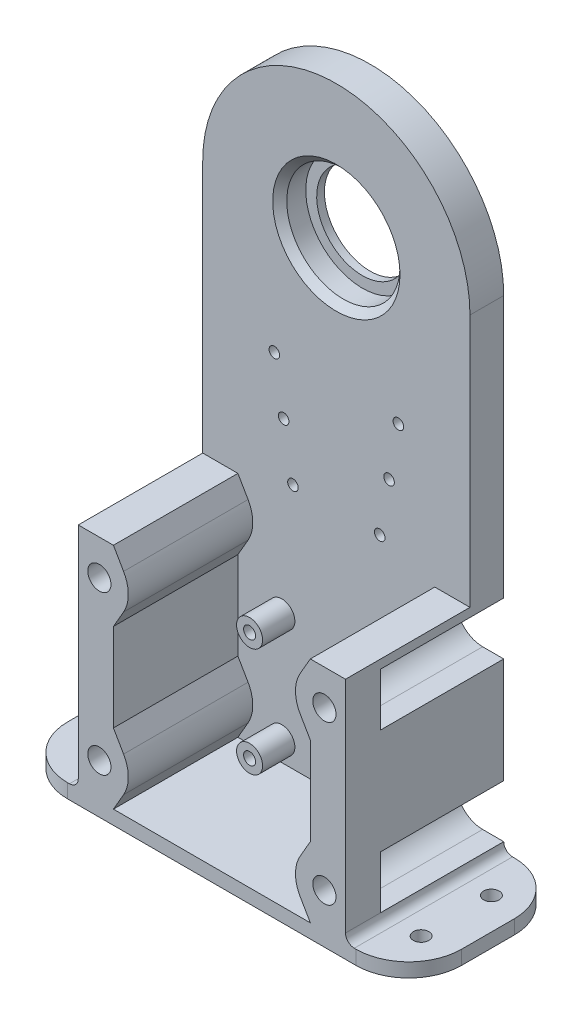
SolidWorks part; units mm, degrees
ref_plane "Ebene vorne" through (0, 0, 0) normal (0, 0, 1) x (1, 0, 0)
ref_plane "Ebene oben" through (0, 0, 0) normal (0, 1, 0) x (1, 0, 0)
ref_plane "Ebene rechts" through (0, 0, 0) normal (1, 0, 0) x (0, 0, -1)
sketch "Skizze1" plane through (0, 0, 0) normal (1, 0, 0) x (0, 0, -1)
  line L1 (-22.5, 65) -> (22.5, 65)
  line L2 (-22.5, 65) -> (-22.5, 0)
  line L3 (-22.5, 0) -> (22.5, 0)
  line L4 (22.5, 65) -> (22.5, 0)
  point P4 (0, 0)
  dimension "D1" = 45
  dimension "D2" = 65
extrude "Aufsatz-Linear austragen1" add sketch "Skizze1" along normal mid plane 76
sketch "Skizze2" plane through (0, 0, 22.5) normal (0, 0, 1) x (1, 0, 0)
  line L0 (-38, 0) -> (-28, 0)
  line L1 (38, 0) -> (-38, 0) construction
  line L2 (-28, 0) -> (-22.2265, 10)
  line L3 (-22.2265, 10) -> (-28, 20)
  line L4 (-28, 20) -> (-28, 45)
  line L5 (-28, 45) -> (-22.2265, 55)
  line L6 (-22.2265, 55) -> (-28, 65)
  line L7 (38, 65) -> (-38, 65) construction
  line L8 (-28, 65) -> (-38, 65)
  line L9 (-38, 65) -> (-38, 0)
  line L10 (-38, 32.5) -> (38, 32.5) construction
  line L11 (38, 65) -> (38, 0) construction
  line L12 (-28, 20) -> (-28, 0) construction
  line L13 (0, 0) -> (0, 65) construction
  line L14 (28, 20) -> (28, 0) construction
  line L15 (38, 65) -> (38, 0)
  line L16 (28, 65) -> (38, 65)
  line L17 (22.2265, 55) -> (28, 65)
  line L18 (28, 45) -> (22.2265, 55)
  line L19 (28, 20) -> (28, 45)
  line L20 (22.2265, 10) -> (28, 20)
  line L21 (28, 0) -> (22.2265, 10)
  line L22 (38, 0) -> (28, 0)
  point P18 (-28, 32.5)
  dimension "D1" = 25
  dimension "D2" = 120
  dimension "D3" = 10
extrude "Schnitt-Linear austragen1" cut sketch "Skizze2" against normal blind 35.4 flip side to cut
sketch "Skizze3" plane through (0, 0, -22.5) normal (0, 0, -1) x (-1, 0, 0)
  line L0 (-32, 17.5) -> (-38, 17.5)
  line L1 (-38, 0) -> (-38, 65) construction
  line L2 (-32, 2.5) -> (-38, 2.5)
  line L3 (-38, 0) -> (38, 0) construction
  line L4 (-38, 17.5) -> (-38, 2.5)
  line L5 (0, 0) -> (0, 65) construction
  line L6 (-38, 65) -> (38, 65) construction
  line L7 (-38, 32.5) -> (38, 32.5) construction
  line L8 (38, 0) -> (38, 65) construction
  line L9 (38, 17.5) -> (38, 2.5)
  line L10 (32, 2.5) -> (38, 2.5)
  line L11 (32, 17.5) -> (38, 17.5)
  line L12 (32, 47.5) -> (38, 47.5)
  line L13 (32, 62.5) -> (38, 62.5)
  line L14 (38, 47.5) -> (38, 62.5)
  line L15 (-38, 47.5) -> (-38, 62.5)
  line L16 (-32, 62.5) -> (-38, 62.5)
  line L17 (-32, 47.5) -> (-38, 47.5)
  arc A0 (-32, 2.5) -> (-32, 17.5) centre (-32, 10) ccw
  arc A1 (32, 2.5) -> (32, 17.5) centre (32, 10) cw
  arc A2 (32, 62.5) -> (32, 47.5) centre (32, 55) ccw
  arc A3 (-32, 62.5) -> (-32, 47.5) centre (-32, 55) cw
  dimension "D1" = 10
  dimension "D2" = 15
  dimension "D3" = 6
extrude "Schnitt-Linear austragen2" cut sketch "Skizze3" against normal blind 35
sketch "Skizze4" plane through (0, 0, 12.5) normal (0, 0, -1) x (-1, 0, 0)
  line L0 (0, 0) -> (0, 65) construction
  line L1 (-38, 0) -> (38, 0) construction
  line L2 (-38, 65) -> (38, 65) construction
  line L3 (-38, 32.5) -> (38, 32.5) construction
  line L4 (-38, 17.5) -> (-38, 47.5) construction
  line L5 (38, 17.5) -> (38, 47.5) construction
  circle A0 centre (32, 10) radius 3.3
  circle A1 centre (-32, 10) radius 3.3
  circle A2 centre (-32, 55) radius 3.3
  circle A3 centre (32, 55) radius 3.3
  dimension "D1" = 6.6
extrude "Schnitt-Linear austragen3" cut sketch "Skizze4" against normal through all
sketch "Skizze5" plane through (0, 0, -12.9) normal (0, 0, 1) x (1, 0, 0)
  line L0 (-38, 65) -> (38, 65)
  line L1 (38, 65) -> (38, 137)
  line L2 (-38, 137) -> (-38, 65)
  arc A0 (38, 137) -> (-38, 137) centre (0, 137) ccw
  dimension "D1" = 110
extrude "Aufsatz-Linear austragen2" add sketch "Skizze5" against normal up to surface (9.6 mm away) up to face at (0, 32.5, -22.5)
sketch "Skizze6" plane through (0, 0, -12.9) normal (0, 0, 1) x (1, 0, 0)
  circle A0 centre (0, 137) radius 16.1
  dimension "D1" = 32.2
extrude "Schnitt-Linear austragen4" cut sketch "Skizze6" against normal blind 7.4
sketch "Skizze8" plane through (0, 0, -22.5) normal (0, 0, -1) x (-1, 0, 0)
  circle A0 centre (0, 137) radius 13
  dimension "D1" = 26
extrude "Schnitt-Linear austragen5" cut sketch "Skizze8" against normal through all
sketch "Skizze9" plane through (0, 0, -22.5) normal (0, 0, -1) x (-1, 0, 0)
  line L0 (0, 0) -> (28.5739, 162.0506) construction
  line L1 (-38, 0) -> (38, 0) construction
  line L2 (0, 0) -> (0, 175) construction
  arc A0 (38, 137) -> (-38, 137) centre (0, 137) ccw construction
  circle A1 centre (12.3429, 70) radius 1.5
  circle A2 centre (14.9878, 85) radius 1.5
  circle A3 centre (17.6327, 100) radius 1.5
  circle A4 centre (-12.3429, 70) radius 1.5
  circle A5 centre (-17.6327, 100) radius 1.5
  circle A6 centre (-14.9878, 85) radius 1.5
  dimension "D2" = 3
  dimension "D1" = 100
  dimension "D3" = 70
  dimension "D4" = 15
  dimension "D5" = 15
extrude "Schnitt-Linear austragen6" cut sketch "Skizze9" against normal through all
sketch "Skizze12" plane through (0, 0, 0) normal (0, -1, 0) x (1, 0, 0)
  line L1 (-38, 22.5) -> (38, 22.5)
  line L2 (-38, 22.5) -> (-38, -22.5)
  line L3 (-38, -22.5) -> (38, -22.5)
  line L4 (38, 22.5) -> (38, -22.5)
extrude "Aufsatz-Linear austragen4" add sketch "Skizze12" along normal blind 4
sketch "Skizze10" plane through (38, 0, 0) normal (1, 0, 0) x (0, 0, -1)
  line L0 (-22.5, 65) -> (-22.5, -4) construction
  line L1 (22.5, -4) -> (-22.5, -4)
  line L2 (22.5, -4) -> (22.5, 0)
  line L3 (22.5, 0) -> (-22.5, 0)
  line L4 (-22.5, -4) -> (-22.5, 0)
  line L5 (22.5, -4) -> (22.5, 2.5) construction
  line L7 (22.5, -4) -> (-22.5, -4) construction
  dimension "D1" = 4
extrude "Aufsatz-Linear austragen3" add sketch "Skizze10" along normal blind 18
fillet "Verrundung1" radius 15 2 edges at (56, -2, 22.5) (56, -2, -22.5)
sketch "Skizze11" plane through (0, 2.5, 0) normal (0, 1, 0) x (1, 0, 0)
  line L0 (56, 0) -> (38, 0) construction
  line L1 (56, 7.5) -> (56, -7.5) construction
  line L2 (38, 12.9) -> (38, -22.5) construction
  line L3 (47, 0) -> (47, 10) construction
  circle A0 centre (47, 10) radius 2.2
  circle A1 centre (47, -10) radius 2.2
  dimension "D1" = 4.4
  dimension "D2" = 10
extrude "Schnitt-Linear austragen7" cut sketch "Skizze11" against normal through all
mirror "Spiegeln1" about plane through (0, 0, 0) normal (1, 0, 0) of "Schnitt-Linear austragen7", "Verrundung1", "Aufsatz-Linear austragen3"
sketch "Skizze13" plane through (0, 0, -12.9) normal (0, 0, 1) x (1, 0, 0)
  line L0 (0, 0) -> (0, 42.3) construction
  line L1 (-9.8972, 21.15) -> (11.2382, 21.15) construction
  circle A0 centre (-15.5, 36.65) radius 1.7
  circle A1 centre (-15.5, 36.65) radius 3.7
  circle A3 centre (15.5, 36.65) radius 1.7
  circle A4 centre (15.5, 36.65) radius 3.7
  circle A5 centre (15.5, 5.65) radius 1.7
  circle A6 centre (15.5, 5.65) radius 3.7
  circle A7 centre (-15.5, 5.65) radius 1.7
  circle A8 centre (-15.5, 5.65) radius 3.7
  point P5 (0.6705, 21.15)
  point P6 (0, 21.15)
  point P24 (0, 21.15)
  dimension "D2" = 31
  dimension "D3" = 31
  dimension "D4" = 3.4
  dimension "D5" = 2
  dimension "D6" = 4
  dimension "D1" = 42.3
extrude "Aufsatz-Linear austragen5" add sketch "Skizze13" along normal up to surface (9.1787 mm away)
chamfer "Fase1" [suppressed] distance 3 angle 60
sketch "Skizze14" plane through (0, 0, -12.9) normal (0, 0, 1) x (1, 0, 0)
  circle A0 centre (-15.5, 5.65) radius 1.7 construction
  circle A1 centre (15.5, 5.65) radius 1.7 construction
  circle A2 centre (15.5, 36.65) radius 1.7 construction
  circle A3 centre (-15.5, 36.65) radius 1.7 construction
  circle A4 centre (-15.5, 5.65) radius 1.7
  circle A5 centre (15.5, 5.65) radius 1.7
  circle A6 centre (15.5, 36.65) radius 1.7
  circle A7 centre (-15.5, 36.65) radius 1.7
extrude "Schnitt-Linear austragen8" cut sketch "Skizze14" against normal up to surface (9.6 mm away) up to face at (-14.9878, 86.5, -22.5)
sketch "Skizze15" plane through (0, 0, -22.5) normal (0, 0, -1) x (-1, 0, 0)
  circle A0 centre (0, 21.15) radius 5
  dimension "D1" = 10
extrude "Schnitt-Linear austragen9" cut sketch "Skizze15" against normal up to surface (9.6 mm away) up to face at (-11.8, 5.65, -12.9)
sketch "Skizze19" plane through (0, 0, -22.5) normal (0, 0, -1) x (-1, 0, 0)
  circle A0 centre (-15.5, 36.65) radius 3.25
  circle A1 centre (15.5, 36.65) radius 3.25
  circle A2 centre (15.5, 5.65) radius 3.25
  circle A3 centre (-15.5, 5.65) radius 3.25
  point P12 (0, 21.15)
  dimension "D1" = 6.5
  dimension "D2" = 4
extrude "Schnitt-Linear austragen11" cut sketch "Skizze19" against normal blind 3.4
fillet "Verrundung2" radius 10 4 edges at (22.2265, 10, 4.8) (22.2265, 55, 4.8) (-22.2265, 55, 4.8) (-22.2265, 10, 4.8)
chamfer "Fase2" distance 2 angle 45 1 edges at (16.1, 137, -12.9)
fillet "Verrundung3" radius 2.5 2 edges at (-38, 0, 0) (38, 0, 0)
